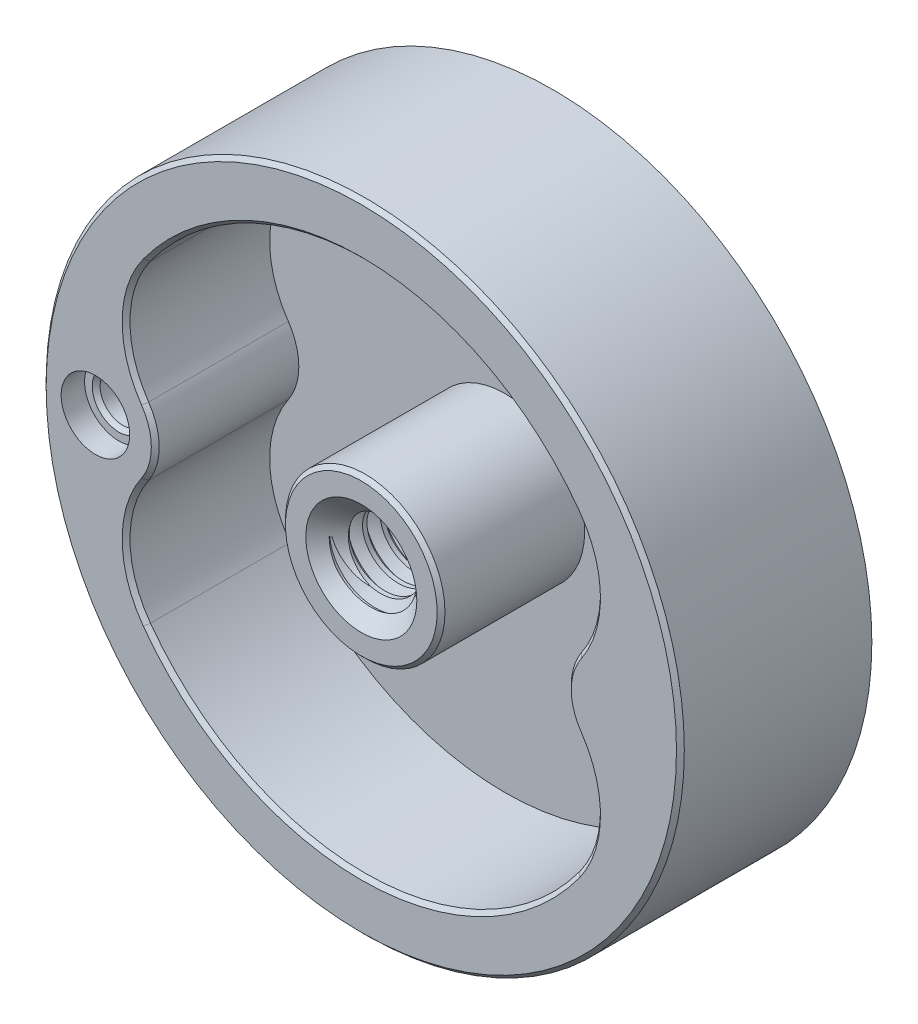
SolidWorks part; units mm, degrees
other "Markup1"
sketch "Sketch14" plane through (50.8, -19.05, 0) normal (0.0411, -0.6216, -0.7823) x (-0.9316, -0.3069, 0.195)
sketch "Sketch17" plane through (50.8, -19.05, 0.2032) normal (0.0411, -0.6216, -0.7823) x (-0.9316, -0.3069, 0.195)
material "Plain Carbon Steel"
ref_plane "Front Plane" through (0, 0, 0) normal (0, 0, 1) x (1, 0, 0)
ref_plane "Top Plane" through (0, 0, 0) normal (0, 1, 0) x (1, 0, 0)
ref_plane "Right Plane" through (0, 0, 0) normal (1, 0, 0) x (0, 0, -1)
sketch "Sketch1" plane through (0, 0, 0) normal (0, 0, 1) x (1, 0, 0)
  circle A0 centre (31.75, 0) radius 19.05
  dimension "D1" = 38.1
extrude "Boss-Extrude1" add sketch "Sketch1" along normal blind 11.43 contours A0
hole_wizard "#6-32 Tapped Hole1" positions "Sketch2" profile "Sketch3" tap size "#6-32" standard "ANSI Inch"
sketch "Sketch2" plane through (0, 0, 11.43) normal (0, 0, 1) x (1, 0, 0)
  line L0 (31.75, 0) -> (15.875, 0) construction
  point P0 (15.875, 0)
  dimension "D1" = 15.875
cosmetic thread "Hole Thread1" parameters "D1"=7.62, "D2"=3.5052
sketch "Sketch3" plane through (15.875, 0, 11.43) normal (1, 0, 0) x (0, -1, 0)
  line L0 (0, 0) -> (0, 9.906)
  line L1 (0, 9.906) -> (1.3525, 9.0933)
  line L2 (1.3525, 9.0933) -> (1.3525, 0)
  line L5 (1.3525, 0) -> (0, 0)
  line L10 (0, 9.906) -> (-1.3526, 9.0933) construction
  line L11 (0, -6.35) -> (0, 107.95) construction
  dimension "Tap Drill Dia." = 2.7051
  dimension "Tap Drill Depth" = 9.906
  dimension "Drill Angle" = 118
sketch "Sketch4" plane through (0, 0, 0) normal (0, 0, -1) x (-1, 0, 0)
  circle A0 centre (-31.75, 0) radius 8.255
  dimension "D1" = 16.51
extrude "Cut-Extrude1" cut sketch "Sketch4" against normal blind 1.27
sketch "Sketch9" plane through (0, 0, 11.43) normal (0, 0, 1) x (1, 0, 0)
  circle A0 centre (15.875, 0) radius 1.9844
  dimension "D1" = 3.9688
sketch "Sketch11" plane through (0, 0, 11.43) normal (0, 0, 1) x (1, 0, 0)
  line L0 (31.75, -1000) -> (31.75, 49000) construction
  arc A0 (16.2768, -3.5492) -> (47.2232, -3.5492) centre (31.75, 0) ccw
  circle A1 centre (31.75, 0) radius 19.05 construction
  arc A2 (16.2768, -3.5492) -> (16.2768, 3.5492) centre (15.875, 0) ccw
  circle A3 centre (31.75, 0) radius 19.05 construction
  circle A6 centre (31.75, 0) radius 4.7625
  arc A7 (47.2232, -3.5492) -> (47.2232, 3.5492) centre (47.625, 0) cw
  arc A8 (47.2232, 3.5492) -> (16.2768, 3.5492) centre (31.75, 0) ccw
  circle A9 centre (39.9268, -0.2781) radius 3.175 construction
  circle A10 centre (15.875, 0) radius 1.9844 construction
  circle A11 centre (31.75, 0) radius 3.175 construction
  dimension "D1" = 3.175
  dimension "D2" = 1.5875
  dimension "D3" = 6.35
  dimension "D4" = 1.5875
  dimension "D5" = 6.35
extrude "Cut-Extrude4" cut sketch "Sketch11" against normal offset from surface (8.5725 mm away) 1.5875 up to face at (23.495, 0, 1.27)
fillet "Fillet1" radius 6.35 4 edges at (47.2232, -3.5492, 7.1437) (47.2232, 3.5492, 7.1437) (16.2768, 3.5492, 7.1437) (16.2768, -3.5492, 7.1437)
sketch "Sketch18" plane through (0, 0, 11.43) normal (0, 0, 1) x (1, 0, 0)
  circle A0 centre (31.75, 0) radius 2.0447
  dimension "D1" = 4.0894
extrude "Cut-Extrude8" cut sketch "Sketch18" against normal through all
sketch "Sketch8" plane through (0, 0, 0) normal (0, 0, -1) x (-1, 0, 0)
  circle A0 centre (-31.75, 0) radius 3.1877
  dimension "D1" = 6.3754
extrude "Counterbore" cut sketch "Sketch8" against normal blind 2.54 contours A0
sketch "Sketch16" plane through (0, 0, 11.43) normal (0, 0, 1) x (1, 0, 0)
  circle A0 centre (15.875, 0) radius 2.0447
  dimension "D1" = 4.0894
extrude "Cut-Extrude7" cut sketch "Sketch16" against normal blind 1.397
chamfer "Chamfer2" distance 0.2337 angle 45 11 edges at (17.2275, 0, 10.033) (36.5125, 0, 11.43) (50.8, 0, 11.43) (45.7938, -5.7061, 11.43) (31.75, -15.875, 11.43) (44.0531, 0, 11.43) (17.7062, -5.7061, 11.43) (45.7938, 5.7061, 11.43) (19.4469, 0, 11.43) (31.75, 15.875, 11.43) (17.7062, 5.7061, 11.43)
chamfer "Chamfer3" distance 1.27 angle 45 1 edges at (33.7947, 0, 11.43)
thread "Thread2" start angle 0, offset 1, length 0, pitch 1.0583, diameter 4.0894
ref_plane "Plane2" through (29.7053, 0, 11.16) normal (0, -1, 0) x (-1, 0, 0)
sketch "Thread Profile2" plane through (29.7053, 0, 11.16) normal (0, -1, 0) x (-1, 0, 0)
  line L0 (0, 0) -> (0, 1.0583) construction
  line L1 (0, 0) -> (0.5728, 0.3307)
  line L2 (0.5728, 0.3307) -> (0.5728, 0.463)
  line L3 (0.5728, 0.463) -> (0, 0.7937)
  line L4 (0.5728, 0.3969) -> (0, 0.3969) construction
  line L11 (0, 0) -> (0, 0.7937)
  point P2 (0, 0)
  dimension "Pitch" = 1.0583
  dimension "Profile_Angle" = 60
  dimension "Profile_Land" = 0.1323
  dimension "Profile_Height" = 0.5728
